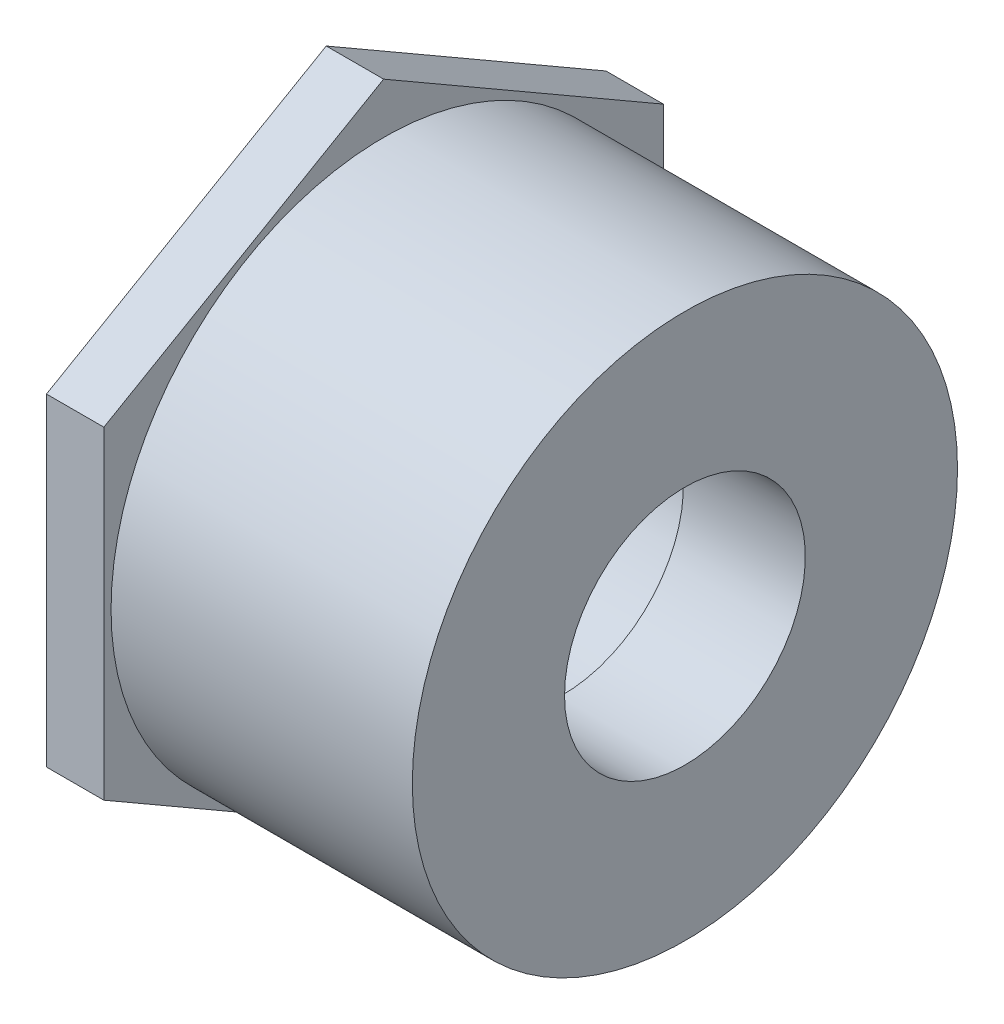
SolidWorks part; units mm, degrees
ref_plane "Front Plane" through (0, 0, 0) normal (0, 0, 1) x (1, 0, 0)
ref_plane "Top Plane" through (0, 0, 0) normal (0, 1, 0) x (1, 0, 0)
ref_plane "Right Plane" through (0, 0, 0) normal (1, 0, 0) x (0, 0, -1)
sketch "Sketch0" plane through (0, 0, 0) normal (0, 0, 1) x (1, 0, 0)
  line L0 (-39.6875, 0) -> (0, 0) construction
  line L2 (-29.3624, 30.1625) -> (-29.3624, -30.1625) construction
  line L3 (-33.3375, 30.9562) -> (-33.3375, -30.9562) construction
  line L5 (-13.4937, 16.637) -> (-39.6875, 16.8275) construction
  line L6 (-13.4937, 16.637) -> (-13.4937, -16.637) construction
  line L7 (-13.4937, -16.637) -> (-39.6875, -16.8275) construction
  line L8 (-39.6875, 16.8275) -> (-39.6875, -16.8275) construction
  line L14 (-13.4937, 13.3223) -> (-13.4937, -13.3223) construction
  line L21 (-39.6875, 0) -> (-13.4937, 0) construction
  point P12 (-29.3624, 0)
  point P27 (-33.3375, 0)
  dimension "A" = 39.6875
  dimension "OD A 2" = 33.655
  dimension "OD B 2" = 33.274
  dimension "ID 2" = 26.6446
  dimension "B" = 13.4937
  dimension "Pipe OD 1" = 60.325
  dimension "C 1" = 29.3624
  dimension "J" = 61.9125
  dimension "K" = 6.35
sketch "Sketch1" plane through (0, 0, 0) normal (0, 0, 1) x (1, 0, 0)
  line L0 (-39.6875, 0) -> (0, 0) construction
  line L1 (-39.6875, 0) -> (0, 0) construction
  line L2 (-39.6875, -30.1625) -> (0, -30.1625)
  line L3 (0, -13.3223) -> (0, -30.1625)
  line L4 (-39.6875, -30.1625) -> (-39.6875, -16.8275)
  line L5 (-39.6875, -16.8275) -> (-13.4937, -16.637)
  line L6 (0, 0) -> (0, -13.3223) construction
  line L8 (-13.4937, -13.3223) -> (-13.4937, -16.637)
  line L11 (-13.4937, -13.3223) -> (0, -13.3223)
revolve "Revolve1" add sketch "Sketch1" angle 360 about L1
sketch "Sketch2" plane through (-39.6875, 0, 0) normal (-1, 0, 0) x (0, 0, 1)
  line L0 (0, 0) -> (0, 35.7452) construction
  line L1 (0, 35.7452) -> (-30.9563, 17.8726)
  line L2 (-30.9563, 17.8726) -> (-30.9563, -17.8726)
  line L3 (-30.9563, -17.8726) -> (0, -35.7452)
  line L4 (0, -35.7452) -> (30.9563, -17.8726)
  line L5 (30.9563, -17.8726) -> (30.9563, 17.8726)
  line L6 (30.9563, 17.8726) -> (0, 35.7452)
  circle A0 centre (0, 0) radius 16.8275 construction
  circle A1 centre (0, 0) radius 16.8275
  circle A2 centre (0, 0) radius 30.9562 construction
  point P3 (0, 30.9562)
extrude "Boss-Extrude1" add sketch "Sketch2" against normal up to vertex (6.35 mm away) up to point (-33.3375, 0, 0)
